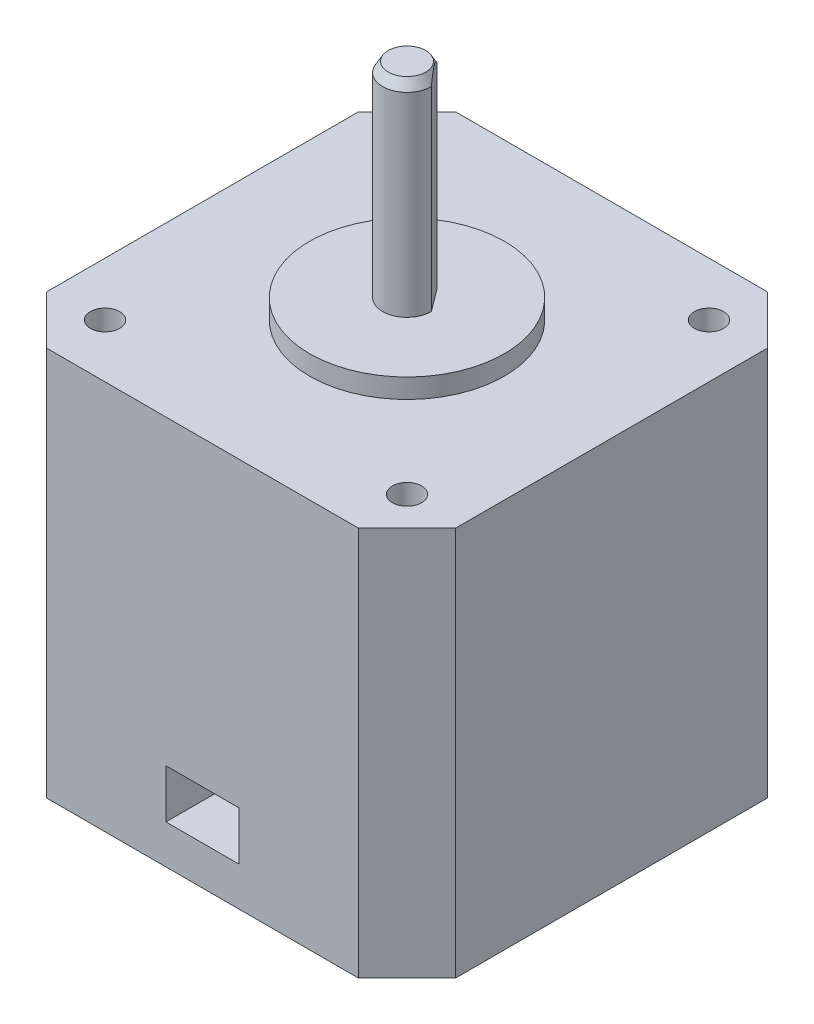
SolidWorks part; units mm, degrees
ref_plane "Front Plane" through (0, 0, 0) normal (0, 0, 1) x (1, 0, 0)
ref_plane "Top Plane" through (0, 0, 0) normal (0, 1, 0) x (1, 0, 0)
ref_plane "Right Plane" through (0, 0, 0) normal (1, 0, 0) x (0, 0, -1)
sketch "Sketch1" plane through (0, 0, 0) normal (0, 1, 0) x (1, 0, 0)
  line L6 (-21, -21) -> (21, -21)
  line L7 (-21, -21) -> (-21, 21)
  line L8 (-21, 21) -> (21, 21)
  line L9 (21, -21) -> (21, 21)
  line L10 (-21, -21) -> (21, 21) construction
  line L11 (-21, 21) -> (21, -21) construction
  point P0 (0, 0)
  dimension "D1" = 42
extrude "Boss-Extrude1" add sketch "Sketch1" along normal blind 40
sketch "Sketch7" plane through (0, 40, 0) normal (0, 1, 0) x (1, 0, 0)
  line L3 (-15.5, -15.5) -> (15.5, -15.5) construction
  line L4 (-15.5, -15.5) -> (-15.5, 15.5) construction
  line L5 (-15.5, 15.5) -> (15.5, 15.5) construction
  line L6 (15.5, -15.5) -> (15.5, 15.5) construction
  line L7 (-15.5, -15.5) -> (15.5, 15.5) construction
  line L8 (-15.5, 15.5) -> (15.5, -15.5) construction
  point P0 (0, 0)
  dimension "D1" = 31
hole_wizard "Ø3.0mm Dowel Hole1" positions "Sketch8" profile "Sketch9" hole size "Ø3.0" standard "ANSI Metric"
sketch "Sketch8" plane through (0, 40, 0) normal (0, 1, 0) x (1, 0, 0)
  point P0 (-15.5, 15.5)
  point P3 (15.5, 15.5)
  point P6 (15.5, -15.5)
  point P9 (-15.5, -15.5)
sketch "Sketch9" plane through (-15.5, 40, -15.5) normal (1, 0, 0) x (0, 0, 1)
  line L0 (0, 0) -> (0, 5.4013)
  line L1 (0, 5.4013) -> (1.5, 4.5)
  line L2 (1.5, 4.5) -> (1.5, 0)
  line L5 (1.5, 0) -> (0, 0)
  line L10 (0, 5.4013) -> (-1.5, 4.5) construction
  line L11 (0, -6.35) -> (0, 107.95) construction
  dimension "Hole Dia." = 3
  dimension "Hole Depth" = 4.5
  dimension "Drill Angle" = 118
sketch "Sketch2" plane through (0, 40, 0) normal (0, 1, 0) x (1, 0, 0)
  line L0 (0, -22) -> (0, 22) construction
  line L1 (-22, 0) -> (22, 0) construction
  circle A0 centre (0, 0) radius 10
  dimension "D1" = 20
extrude "Boss-Extrude2" add sketch "Sketch2" along normal blind 2
sketch "Sketch4" plane through (0, 40, 0) normal (0, 1, 0) x (1, 0, 0)
  line L0 (0.7, 2.4) -> (2.5, 0)
  line L1 (-22, 0) -> (22, 0) construction
  arc A0 (0.7, 2.4) -> (2.5, 0) centre (0, 0) ccw
  arc A1 (2.5, 0) -> (0.7, 2.4) centre (0, 0) ccw construction
  dimension "D1" = 5
  dimension "D2" = 2
extrude "Boss-Extrude3" add sketch "Sketch4" along normal blind 23
sketch "Sketch10" plane through (0, 0, 21) normal (0, 0, 1) x (1, 0, 0)
  line L1 (-3.75, 4) -> (3.75, 4)
  line L2 (-3.75, 4) -> (-3.75, 9)
  line L3 (-3.75, 9) -> (3.75, 9)
  line L4 (3.75, 4) -> (3.75, 9)
  line L5 (0, -23.1) -> (0, 23.1) construction
  line L6 (23.1, 0) -> (-23.1, 0) construction
  point P6 (0, 9)
  dimension "D1" = 5
  dimension "D2" = 7.5
  dimension "D3" = 4
extrude "Cut-Extrude1" cut sketch "Sketch10" against normal blind 5
chamfer "Chamfer1" distance 1 angle 30 1 edges at (-2, 63, 1.5) first distance on face at (-0.2, 52.5, 0.15)
chamfer "Chamfer2" distance 5 angle 45 4 edges at (-21, 20, 21) (21, 20, 21) (-21, 20, -21) (21, 20, -21)
